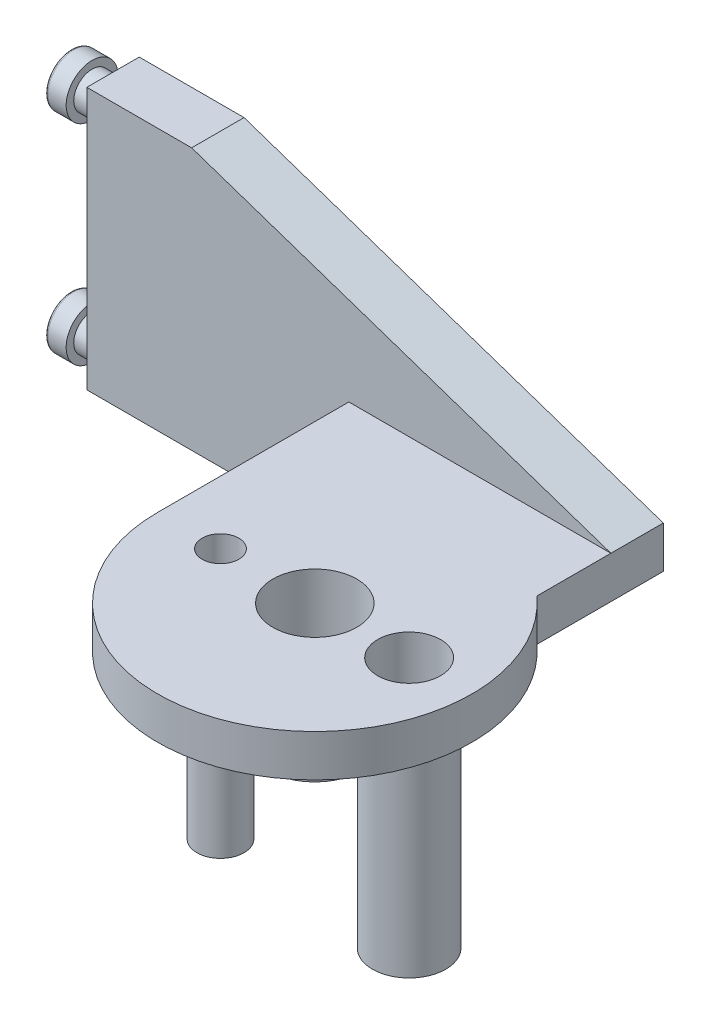
SolidWorks part; units mm, degrees
ref_plane "Front Plane" through (0, 0, 0) normal (0, 0, 1) x (1, 0, 0)
ref_plane "Top Plane" through (0, 0, 0) normal (0, 1, 0) x (1, 0, 0)
ref_plane "Right Plane" through (0, 0, 0) normal (1, 0, 0) x (0, 0, -1)
sketch "Sketch3" plane through (0, 0, 0) normal (0, 0, 1) x (1, 0, 0)
  line L0 (-50, 25) -> (50, 25)
  line L1 (50, 25) -> (50, -25)
  line L2 (50, -25) -> (-50, -25)
  line L3 (-50, -25) -> (-50, 25)
  dimension "D1" = 50
  dimension "D2" = 100
  dimension "D3" = 25
  dimension "D4" = 50
extrude "Boss-Extrude1" add sketch "Sketch3" along normal blind 10
sketch "Sketch4" plane through (-50, 0, 0) normal (-1, 0, 0) x (0, 0, 1)
  line L0 (10, -25) -> (0, -25) construction
  line L1 (10, 25) -> (10, -25) construction
  circle A0 centre (5, 20) radius 3.5
  circle A1 centre (5, -20) radius 3.5
  dimension "D1" = 7
  dimension "D2" = 7
  dimension "D3" = 40
  dimension "D4" = 5
  dimension "D5" = 5
extrude "Boss-Extrude2" add sketch "Sketch4" along normal blind 4
sketch "Sketch5" plane through (-54, 0, 0) normal (-1, 0, 0) x (0, 0, 1)
  circle A0 centre (5, 20) radius 4.95
  circle A1 centre (5, -20) radius 4.95
  dimension "D1" = 9.9
  dimension "D2" = 9.9
extrude "Boss-Extrude3" add sketch "Sketch5" along normal blind 4
sketch "Sketch6" plane through (0, 25, 0) normal (0, 1, 0) x (1, 0, 0)
  line L0 (-50, -10) -> (-50, 0) construction
  line L1 (-50, -1.5) -> (-50, -8.5) construction
  line L2 (0, -46.5) -> (0, -10)
  line L3 (50, -10) -> (-50, -10) construction
  line L4 (0, -10) -> (50, -10)
  line L5 (50, -10) -> (50, -24.1393)
  arc A0 (0, -46.5) -> (50, -24.1393) centre (30, -46.5) ccw
  point P6 (-50, -5)
  dimension "D3" = 60
  dimension "D1" = 80
  dimension "D2" = 41.5
extrude "Boss-Extrude4" add sketch "Sketch6" against normal blind 50
sketch "Sketch7" plane through (0, 25, 0) normal (0, 1, 0) x (1, 0, 0)
  circle A0 centre (30, -46.5) radius 8
  dimension "D1" = 16
extrude "Cut-Extrude1" cut sketch "Sketch7" against normal through all both and the other way through all
sketch "Sketch10" plane through (0, 0, 0) normal (-1, 0, 0) x (0, 0, 1)
  line L0 (10, 25) -> (76.5, 25)
  line L1 (76.5, 25) -> (76.5, -2)
  line L2 (76.5, -25) -> (76.5, 25) construction
  line L3 (76.5, -2) -> (10, -2)
  line L4 (10, -25) -> (10, 25) construction
  line L5 (10, -2) -> (10, 25)
  dimension "D1" = 27
extrude "Cut-Extrude2" cut sketch "Sketch10" against normal through all and the other way through all
sketch "Sketch11" plane through (0, 0, 10) normal (0, 0, 1) x (1, 0, 0)
  line L0 (50, -2) -> (-30, 25)
  line L1 (50, 25) -> (-50, 25) construction
  line L2 (-30, 25) -> (50, 25)
  line L3 (50, 25) -> (50, -2)
  dimension "D1" = 80
extrude "Cut-Extrude3" cut sketch "Sketch11" against normal through all
sketch "Sketch12" plane through (0, 0, 0) normal (-1, 0, 0) x (0, 0, 1)
  line L0 (10, -25) -> (10, -10)
  line L1 (10, -25) -> (10, -2) construction
  line L2 (10, -10) -> (76.5, -10)
  line L3 (76.5, -25) -> (76.5, -2) construction
  line L4 (76.5, -10) -> (76.5, -25)
  line L5 (76.5, -25) -> (10, -25)
  dimension "D1" = 15
extrude "Cut-Extrude4" cut sketch "Sketch12" against normal through all
sketch "Sketch13" plane through (0, 0, 10) normal (0, 0, 1) x (1, 0, 0)
  line L0 (50, -10) -> (-18, -25)
  line L1 (-50, -25) -> (50, -25) construction
  line L2 (-18, -25) -> (50, -25)
  line L3 (50, -25) -> (50, -10)
  dimension "D1" = 68
extrude "Cut-Extrude5" cut sketch "Sketch13" against normal through all
sketch "Sketch15" plane through (0, -2, 0) normal (0, 1, 0) x (1, 0, 0)
  line L1 (0, -10) -> (0, -46.5) construction
  circle A0 centre (12, -46.5) radius 3.5
  circle A1 centre (48, -46.5) radius 6
  dimension "D2" = 7
  dimension "D3" = 12
  dimension "D1" = 12
  dimension "D4" = 36
extrude "Cut-Extrude6" cut sketch "Sketch15" against normal through all
sketch "Sketch16" plane through (0, -10, 0) normal (0, -1, 0) x (-1, 0, 0)
  circle A0 centre (-12, -46.5) radius 4.5
  circle A1 centre (-48, -46.5) radius 7
  dimension "D1" = 9
  dimension "D2" = 14
extrude "Boss-Extrude5" add sketch "Sketch16" along normal blind 40
sketch "Sketch17" plane through (0, -10, 0) normal (0, 1, 0) x (1, 0, 0)
  circle A0 centre (48, -46.5) radius 6
  circle A1 centre (12, -46.5) radius 3.5
  dimension "D1" = 7
  dimension "D2" = 12
extrude "Cut-Extrude7" cut sketch "Sketch17" against normal through all
sketch "Sketch18" plane through (0, -10, 0) normal (0, -1, 0) x (1, 0, 0)
  circle A0 centre (30, 46.5) radius 9.25
  dimension "D1" = 18.5
extrude "Boss-Extrude6" add sketch "Sketch18" along normal blind 15
sketch "Sketch19" plane through (0, -25, 0) normal (0, -1, 0) x (1, 0, 0)
  circle A0 centre (30, 46.5) radius 8
  dimension "D1" = 16
extrude "Cut-Extrude8" cut sketch "Sketch19" against normal through all
fillet "Fillet3" radius 2 3 edges at (12, -10, 51) (30, -10, 55.75) (48, -10, 53.5)
fillet "Fillet4" radius 0.5 2 edges at (-58, -20, 9.95) (-58, 20, 9.95)
